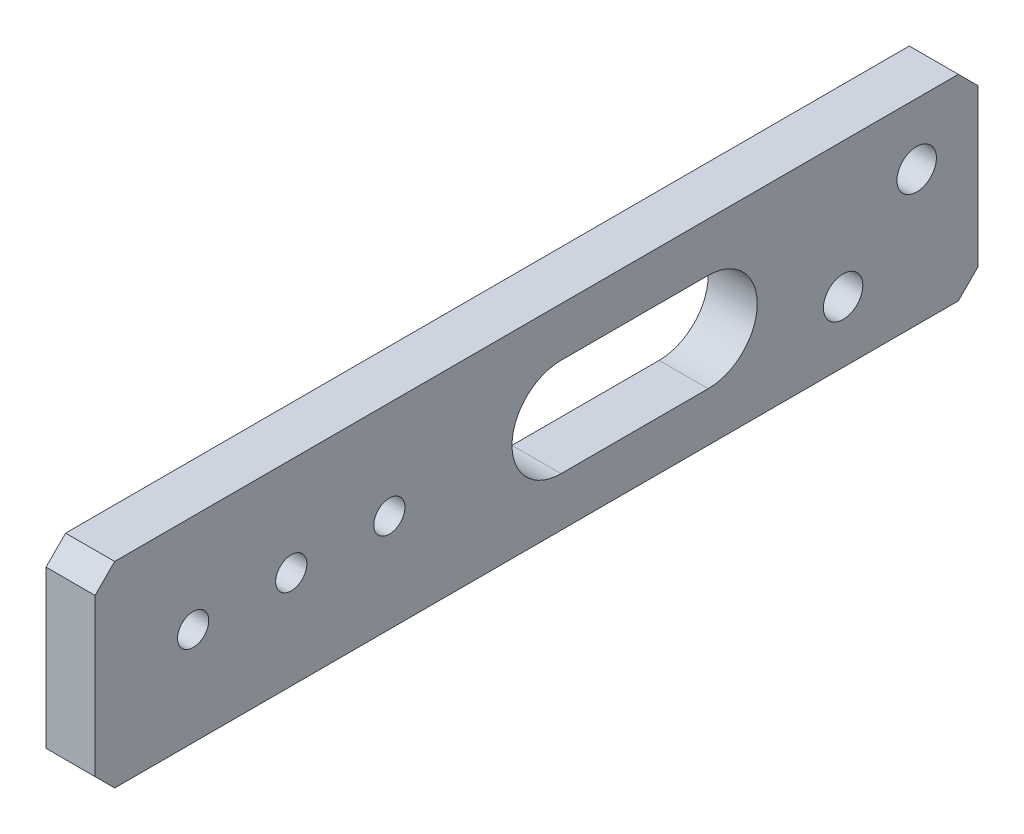
SolidWorks part; units mm, degrees
material "6061-T6 (SS)"
ref_plane "Front" through (0, 0, 0) normal (0, 0, 1) x (1, 0, 0)
ref_plane "Top" through (0, 0, 0) normal (0, 1, 0) x (1, 0, 0)
ref_plane "Right" through (0, 0, 0) normal (1, 0, 0) x (0, 0, -1)
sketch "Sketch1" plane through (0, 0, 0) normal (1, 0, 0) x (0, 0, -1)
  line L1 (0, 0) -> (114.3, 0)
  line L2 (0, 0) -> (0, 25.4)
  line L3 (0, 25.4) -> (114.3, 25.4)
  line L6 (114.3, 25.4) -> (114.3, 0)
  dimension "D1" = 25.4
  dimension "D2" = 114.3
extrude "Boss-Extrude1" add sketch "Sketch1" along normal blind 6.35
hole_wizard "#10-32 Tapped Hole1" positions "Sketch2" profile "Sketch3" tap size "#10-32" standard "ANSI Inch" end condition through all
sketch "Sketch2" plane through (6.35, 0, 0) normal (1, 0, 0) x (0, 0, -1)
  line L0 (0, 0) -> (12.7, 12.7) construction
  line L1 (12.7, 12.7) -> (25.4, 12.7) construction
  line L2 (25.4, 12.7) -> (38.1, 12.7) construction
  line L3 (38.1, 12.7) -> (50.8, 25.4) construction
  line L4 (114.3, 25.4) -> (0, 25.4) construction
  line L6 (0, 25.4) -> (0, 0) construction
  point P0 (12.7, 12.7)
  point P2 (25.4, 12.7)
  point P4 (38.1, 12.7)
  dimension "D1" = 50.8
  dimension "D2" = 12.7
sketch "Sketch3" plane through (6.35, 12.7, -12.7) normal (0, 1, 0) x (0, 0, -1)
  line L0 (0, 0) -> (0, 6.35)
  line L1 (0, 6.35) -> (2.0193, 6.35)
  line L2 (2.0193, 6.35) -> (2.0193, 0)
  line L5 (2.0193, 0) -> (0, 0)
  line L11 (0, -6.35) -> (0, 107.95) construction
  dimension "Thru Tap Drill Dia." = 4.0386
  dimension "Thru Tap Drill Depth" = 6.35
cosmetic thread "Hole Thread1" parameters "D2"=4.826
cosmetic thread "Hole Thread2" parameters "D2"=4.826
cosmetic thread "Hole Thread3" parameters "D2"=4.826
hole_wizard "#10 Clearance Hole1" positions "Sketch4" profile "Sketch5" hole size "#10" standard "ANSI Inch" end condition through all
sketch "Sketch4" plane through (6.35, 0, 0) normal (1, 0, 0) x (0, 0, -1)
  line L0 (88.9, 0) -> (96.8375, 7.9375) construction
  line L1 (0, 0) -> (114.3, 0) construction
  line L2 (96.8375, 7.9375) -> (106.3625, 17.4625) construction
  line L3 (106.3625, 17.4625) -> (114.3, 25.4) construction
  line L5 (114.3, 0) -> (114.3, 25.4) construction
  point P13 (106.3625, 17.4625)
  point P15 (96.8375, 7.9375)
  dimension "D1" = 25.4
  dimension "D2" = 9.525
sketch "Sketch5" plane through (6.35, 17.4625, -106.3625) normal (0, 1, 0) x (0, 0, -1)
  line L0 (0, 0) -> (0, 6.35)
  line L1 (0, 6.35) -> (2.5527, 6.35)
  line L2 (2.5527, 6.35) -> (2.5527, 0)
  line L5 (2.5527, 0) -> (0, 0)
  line L11 (0, -6.35) -> (0, 107.95) construction
  dimension "Thru Hole Dia." = 5.1054
  dimension "Thru Hole Depth" = 6.35
chamfer "Chamfer1" distance 2.54 angle 45 4 edges at (3.175, 25.4, 0) (3.175, 25.4, -114.3) (3.175, 0, -114.3) (3.175, 0, 0)
sketch "Sketch6" plane through (6.35, 0, 0) normal (1, 0, 0) x (0, 0, -1)
  line L0 (79.375, 12.7) -> (60.325, 12.7) construction
  line L1 (79.375, 6.35) -> (60.325, 6.35)
  line L2 (79.375, 19.05) -> (60.325, 19.05)
  line L3 (2.54, 0) -> (111.76, 0) construction
  line L4 (0, 22.86) -> (0, 2.54) construction
  line L5 (114.3, 2.54) -> (114.3, 22.86) construction
  arc A0 (79.375, 6.35) -> (79.375, 19.05) centre (79.375, 12.7) ccw
  arc A1 (60.325, 19.05) -> (60.325, 6.35) centre (60.325, 12.7) ccw
  point P2 (69.85, 12.7)
  dimension "D3" = 53.975
  dimension "D1" = 12.7
  dimension "D2" = 12.7
  dimension "D4" = 28.575
extrude "Cut-Extrude1" cut sketch "Sketch6" against normal through all
